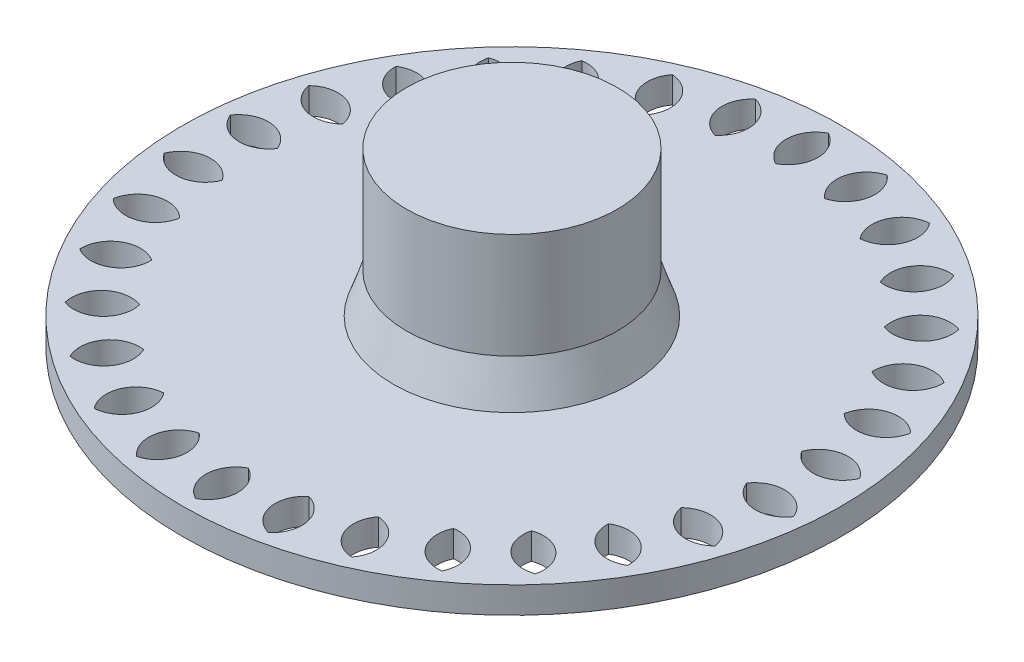
SolidWorks part; units mm, degrees
ref_plane "Front Plane" through (0, 0, 0) normal (0, 0, 1) x (1, 0, 0)
ref_plane "Top Plane" through (0, 0, 0) normal (0, 1, 0) x (1, 0, 0)
ref_plane "Right Plane" through (0, 0, 0) normal (1, 0, 0) x (0, 0, -1)
sketch "Sketch1" plane through (0, 0, 0) normal (0, 1, 0) x (1, 0, 0)
  line L0 (0, 24) -> (0, 20) construction
  arc A1 (0, 20) -> (0, 24) centre (1.0514, 22) cw
  arc A2 (0, 20) -> (0, 24) centre (-1.0514, 22) ccw
  dimension "D1" = 20
  dimension "D2" = 4
sketch "Sketch2" plane through (0, 0, 0) normal (0, 1, 0) x (1, 0, 0)
  circle A0 centre (0, 0) radius 25
  dimension "D1" = 50
extrude "Boss-Extrude1" add sketch "Sketch2" along normal blind 2
extrude "Cut-Extrude1" cut sketch "Sketch1" along normal through all
pattern_circular "CirPattern1" count 30 over 360 about axis through (0, 2, 0) along (0, -1, 0) of "Cut-Extrude1"
sketch "Sketch4" plane through (0, 0, 0) normal (0, 0, 1) x (1, 0, 0)
  line L1 (-8, 5) -> (0, 5)
  line L2 (0, 5) -> (0, 2)
  line L3 (25, 2) -> (-25, 2) construction
  line L5 (-9, 2) -> (0, 2)
  line L6 (-8, 5) -> (-9, 2)
  dimension "D1" = 3
  dimension "D2" = 8
  dimension "D3" = 9
revolve "Revolve1" add sketch "Sketch4" angle 360 about L2
sketch "Sketch5" plane through (0, 5, 0) normal (0, 1, 0) x (1, 0, 0)
  circle A0 centre (0, 0) radius 8
extrude "Boss-Extrude2" add sketch "Sketch5" along normal blind 8
